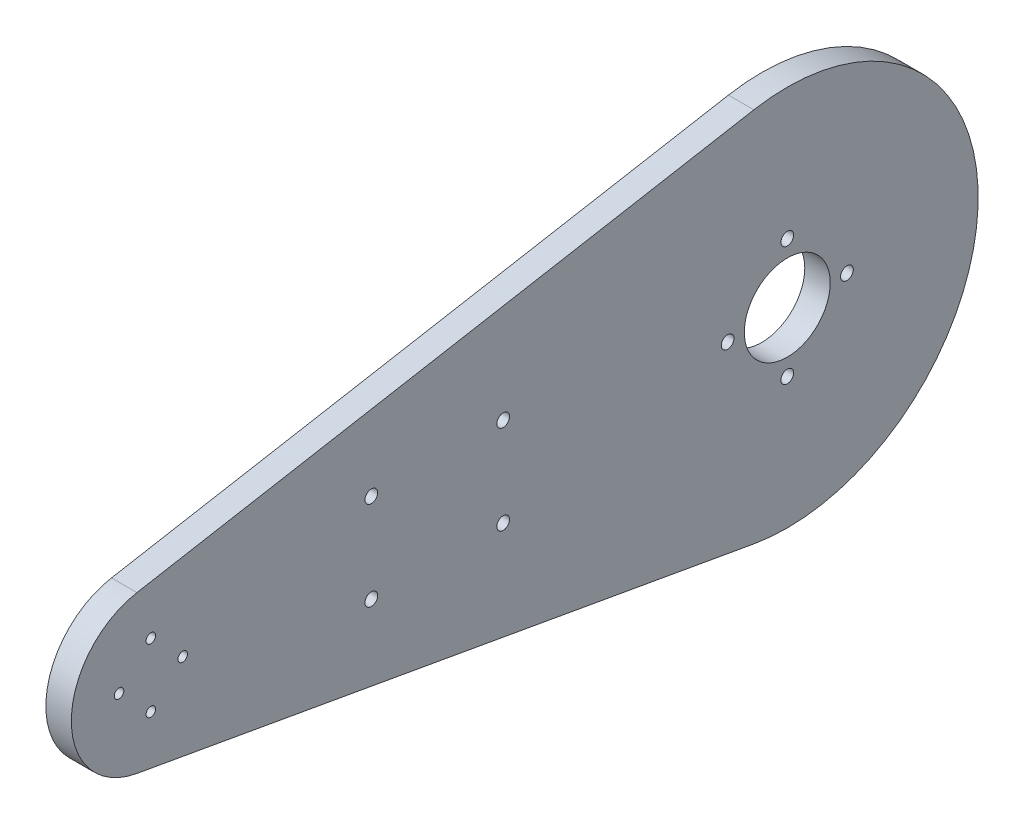
SolidWorks part; units mm, degrees
material "2024-T4"
ref_plane "Front Plane" through (0, 0, 0) normal (0, 0, 1) x (1, 0, 0)
ref_plane "Top Plane" through (0, 0, 0) normal (0, 1, 0) x (1, 0, 0)
ref_plane "Right Plane" through (0, 0, 0) normal (1, 0, 0) x (0, 0, -1)
sketch "Sketch1" plane through (0, 0, 0) normal (1, 0, 0) x (0, 0, -1)
  line L0 (0, 0) -> (-200, 0) construction
  line L1 (-204.375, 24.6142) -> (-10.5, 59.0741)
  line L2 (-204.375, -24.6142) -> (-10.5, -59.0741)
  circle A0 centre (0, 0) radius 13.5
  arc A1 (-10.5, -59.0741) -> (-10.5, 59.0741) centre (0, 0) ccw
  arc A2 (-204.375, 24.6142) -> (-204.375, -24.6142) centre (-200, 0) ccw
  dimension "D1" = 120
  dimension "D2" = 27
  dimension "D3" = 25
  dimension "D5" = 200
extrude "Boss-Extrude1" add sketch "Sketch1" along normal mid plane 8
sketch "Sketch2" plane through (4, 0, 0) normal (1, 0, 0) x (0, 0, -1)
  line L0 (0, 0) -> (0, 18.75) construction
  line L1 (-200, 0) -> (-210, 0) construction
  circle A0 centre (0, 18.75) radius 2
  circle A1 centre (18.75, 0) radius 2
  circle A2 centre (0, -18.75) radius 2
  circle A3 centre (-18.75, 0) radius 2
  circle A4 centre (-200, 0) radius 10 construction
  circle A5 centre (-210, 0) radius 1.5
  circle A6 centre (-200, 10) radius 1.5
  circle A7 centre (-190, 0) radius 1.5
  circle A8 centre (-200, -10) radius 1.5
  point P13 (0, 0)
  point P24 (-200, 0)
  dimension "D1" = 4
  dimension "D6" = 20
  dimension "D7" = 3
  dimension "D2" = 18.75
  dimension "D4" = 18.75
  dimension "D5" = 18.75
  dimension "D9" = 20
  dimension "D10" = 10
  dimension "D3" = 4
  dimension "D8" = 4
extrude "Cut-Extrude1" cut sketch "Sketch2" against normal through all
sketch "Sketch3" plane through (4, 0, 0) normal (1, 0, 0) x (0, 0, -1)
  line L0 (0, 0) -> (-200, 0) construction
  line L1 (-110, 0) -> (-110, 25) construction
  circle A0 centre (-110, 0) radius 25 construction
  circle A1 centre (-89.2877, 14) radius 2
  circle A2 centre (-89.2877, -14) radius 2
  circle A3 centre (-130.7123, 14) radius 2
  circle A4 centre (-130.7123, -14) radius 2
  dimension "D1" = 110
  dimension "D2" = 50
  dimension "D3" = 4
  dimension "D4" = 14
extrude "Cut-Extrude2" cut sketch "Sketch3" against normal through all
equation "\"D4@Sketch2\"=\"D2@Sketch2\""
equation "\"D5@Sketch2\"=\"D2@Sketch2\""
equation "\"shaft-diameter\"=20mm"
equation "\"key-length\"=12mm"
equation "\"key-width\"=4mm"
equation "\"flippershaft-wormgear-diameter\"= 35mm"
equation "\"shaft-ring-groove-depth\"=0.5mm"
equation "\"shaft-ring-groove-width\"= 1.3mm"
equation "\"mini-shaft-diameter\"= 12mm"
equation "\"mini-flipper-shaft-diameter\"= 26mm"
